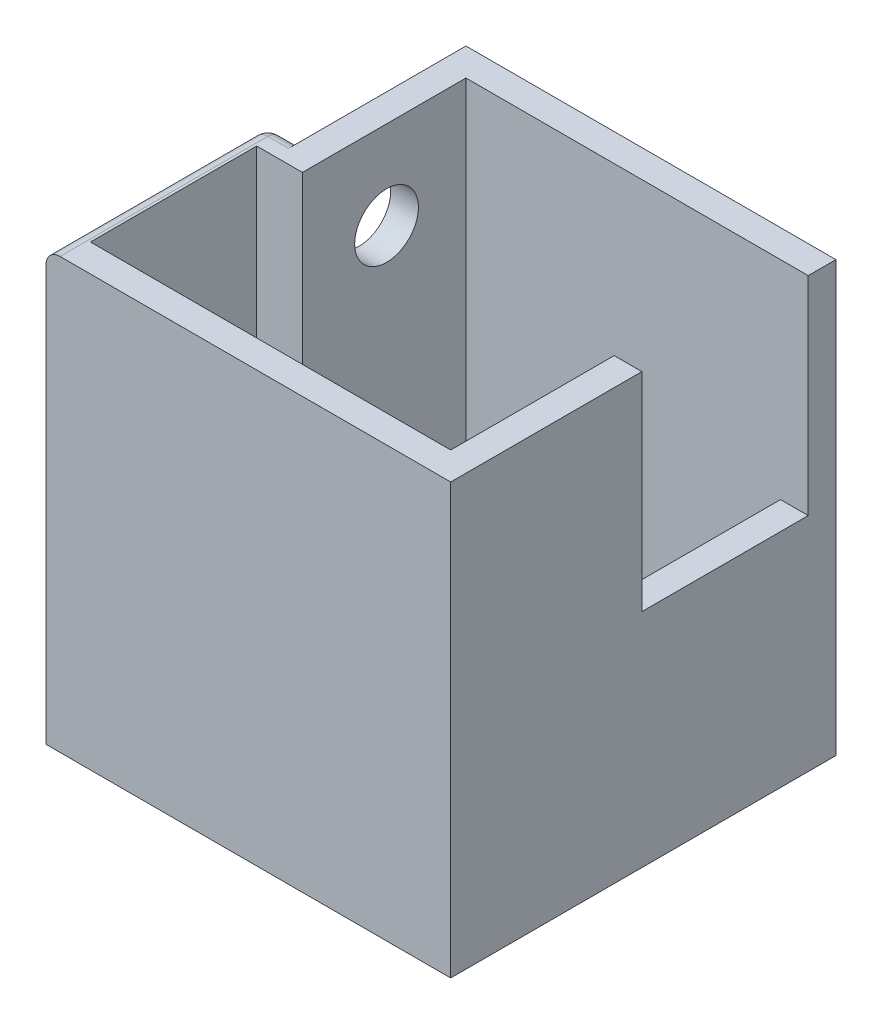
SolidWorks part; units mm, degrees
ref_plane "Plan de face" through (0, 0, 0) normal (0, 0, 1) x (1, 0, 0)
ref_plane "Plan de dessus" through (0, 0, 0) normal (0, 1, 0) x (1, 0, 0)
ref_plane "Plan de droite" through (0, 0, 0) normal (1, 0, 0) x (0, 0, -1)
sketch "Esquisse1" plane through (0, 0, 0) normal (0, 0, 1) x (1, 0, 0)
  line L1 (0, 0) -> (30, 0)
  line L2 (0, 0) -> (0, 31)
  line L3 (0, 31) -> (30, 31)
  line L4 (30, 0) -> (30, 31)
  dimension "D1" = 31
  dimension "D2" = 30
extrude "Boss.-Extru.1" add sketch "Esquisse1" along normal blind 27.8
shell "Coque1" thickness 2 removed face at (15, 31, 13.9)
sketch "Esquisse2" plane through (30, 0, 0) normal (1, 0, 0) x (0, 0, -1)
  line L0 (0, 31) -> (-2, 31) construction
  line L1 (-27.8, 31) -> (0, 31) construction
  line L3 (-2, 31) -> (-14, 31)
  line L4 (-2, 31) -> (-2, 16)
  line L5 (-2, 16) -> (-14, 16)
  line L6 (-14, 31) -> (-14, 16)
  dimension "D1" = 2
  dimension "D2" = 12
  dimension "D3" = 15
extrude "Enlèv. mat.-Extru.1" cut sketch "Esquisse2" against normal up to next
sketch "Esquisse3" plane through (0, 2, 0) normal (0, 1, 0) x (1, 0, 0)
  line L0 (0, -27.8) -> (0, 0) construction
  line L1 (4.1, -25.8) -> (19.1, -25.8)
  line L2 (4.1, -25.8) -> (4.1, -13.8)
  line L3 (4.1, -13.8) -> (19.1, -13.8)
  line L4 (19.1, -25.8) -> (19.1, -13.8)
  line L5 (0, -27.8) -> (30, -27.8) construction
  dimension "D1" = 15
  dimension "D2" = 12
  dimension "D3" = 4.1
  dimension "D4" = 2
extrude "Enlèv. mat.-Extru.2" cut sketch "Esquisse3" against normal up to next
sketch "Esquisse4" plane through (0, 2, 0) normal (0, 1, 0) x (1, 0, 0)
  line L0 (0, -27.8) -> (0, 0) construction
  line L1 (2, -13.8) -> (28, -13.8)
  line L2 (2, -13.8) -> (2, -2)
  line L3 (2, -2) -> (28, -2)
  line L4 (28, -13.8) -> (28, -2)
  dimension "D1" = 2
  dimension "D2" = 11.8
extrude "Boss.-Extru.2" add sketch "Esquisse4" along normal blind 1.5
sketch "Esquisse5" plane through (2, 0, 0) normal (1, 0, 0) x (0, 0, -1)
  line L1 (-13.8, 3.5) -> (-2, 3.5)
  line L2 (-13.8, 3.5) -> (-13.8, 31)
  line L3 (-13.8, 31) -> (-2, 31)
  line L4 (-2, 3.5) -> (-2, 31)
extrude "Boss.-Extru.3" add sketch "Esquisse5" along normal blind 3.3
sketch "Esquisse6" plane through (0, 2, 0) normal (0, 1, 0) x (1, 0, 0)
  line L1 (2, -13.8) -> (4.1, -13.8)
  line L2 (2, -13.8) -> (2, -25.8)
  line L3 (2, -25.8) -> (4.1, -25.8)
  line L4 (4.1, -13.8) -> (4.1, -25.8)
extrude "Boss.-Extru.4" add sketch "Esquisse6" along normal blind 6.3
sketch "Esquisse8" plane through (0, 0, 0) normal (-1, 0, 0) x (0, 0, 1)
  line L1 (0, 0) -> (11.8, 0)
  line L2 (0, 0) -> (0, 31)
  line L3 (0, 31) -> (11.8, 31)
  line L4 (11.8, 0) -> (11.8, 31)
  dimension "D1" = 11.8
extrude "Enlèv. mat.-Extru.3" cut sketch "Esquisse8" against normal blind 3.3
sketch "Esquisse10" plane through (3.3, 0, 0) normal (-1, 0, 0) x (0, 0, 1)
  line L0 (0, 0) -> (11.8, 0) construction
  circle A0 centre (7.73, 24.64) radius 2.3
  point P0 (7.73, 0)
  dimension "D2" = 4.6
  dimension "D1" = 7.73
  dimension "D3" = 24.64
extrude "Enlèv. mat.-Extru.4" cut sketch "Esquisse10" against normal up to next contours A0
sketch "Esquisse14" plane through (0, 31, 0) normal (0, 1, 0) x (1, 0, 0)
  line L0 (30, -27.8) -> (0, -27.8) construction
  line L1 (0, -11.8) -> (0.8, -11.8)
  line L2 (0, -11.8) -> (0, -27.8)
  line L3 (0, -27.8) -> (0.8, -27.8)
  line L4 (0.8, -11.8) -> (0.8, -27.8)
  dimension "D1" = 0.8
extrude "Enlèv. mat.-Extru.5" cut sketch "Esquisse14" against normal up to next
fillet "Congé2" radius 1 1 edges at (2.05, 31, 11.8)
fillet "Congé3" radius 1 3 edges at (0.8, 15, 11.8) (0.8, 30.7071, 12.0929) (0.8, 31, 20.3)
